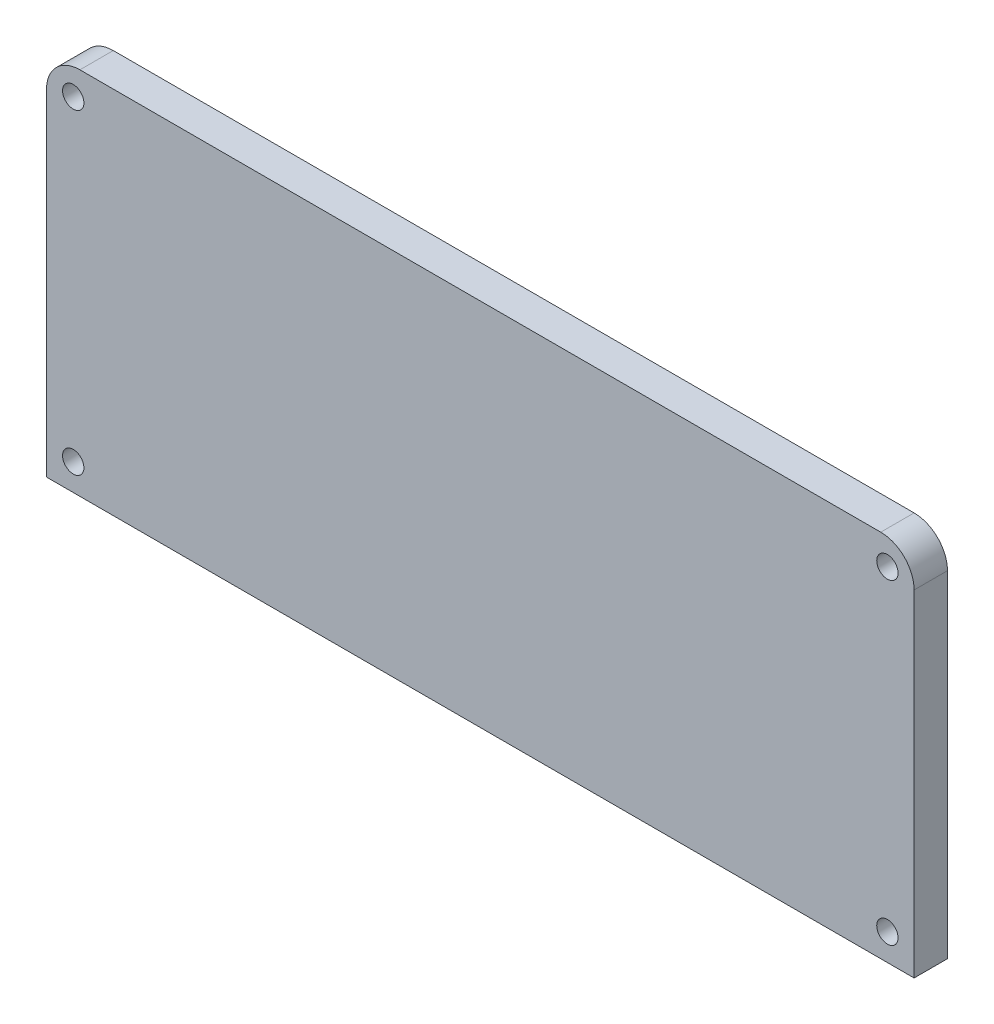
SolidWorks part; units mm, degrees
ref_plane "Front Plane" through (0, 0, 0) normal (0, 0, 1) x (1, 0, 0)
ref_plane "Top Plane" through (0, 0, 0) normal (0, 1, 0) x (1, 0, 0)
ref_plane "Right Plane" through (0, 0, 0) normal (1, 0, 0) x (0, 0, -1)
sketch "Sketch2" plane through (0, 0, 0) normal (1, 0, 0) x (0, 0, -1)
  line L0 (0, 0) -> (0, 20)
  line L1 (0, 20) -> (35.3553, 55.3553)
  line L2 (35.3553, 55.3553) -> (120, 55.3553)
  line L3 (120, 55.3553) -> (120, 0)
  line L4 (120, 0) -> (0, 0)
  dimension "D1" = 20
  dimension "D2" = 50
  dimension "D3" = 135
  dimension "D4" = 120
extrude "Boss-Extrude1" add sketch "Sketch2" along normal blind 130
shell "Shell1" thickness 5 removed face at (65, 27.6777, -120)
sketch "Sketch3" plane through (0, 10, 10) normal (0, 0.7071, 0.7071) x (1, 0, 0)
  line L0 (0, 64.1421) -> (0, 14.1421) construction
  line L1 (17, 52.3921) -> (90.1, 52.3921)
  line L2 (17, 52.3921) -> (17, 25.8921)
  line L3 (17, 25.8921) -> (90.1, 25.8921)
  line L4 (90.1, 52.3921) -> (90.1, 25.8921)
  circle A0 centre (108.1, 39.1421) radius 3.4
  point P6 (0, 39.1421)
  point P7 (17, 39.1421)
  point P11 (90.1, 39.1421)
  dimension "D3" = 6.8
  dimension "D1" = 73.1
  dimension "D2" = 26.5
  dimension "D4" = 18
  dimension "D5" = 17
extrude "Cut-Extrude1" cut sketch "Sketch3" against normal up to surface (5 mm away) up to face at (65, 34.1421, -21.2132)
fillet "Fillet1" radius 10 5 edges at (65, 20, 0) (65, 55.3553, -35.3553) (65, 50.3553, -37.4264) (65, 5, -5) (65, 17.9289, -5)
fillet "Fillet2" radius 5 10 edges at (0, 55.3553, -79.7487) (0, 54.5941, -35.6706) (0, 37.6777, -17.6777) (0, 19.6847, -0.7612) (130, 55.3553, -79.7487) (130, 54.5941, -35.6706) (130, 37.6777, -17.6777) (130, 19.6847, -0.7612) (0, 7.9289, 0) (130, 7.9289, 0)
sketch "Sketch4" plane through (130, 0, 0) normal (1, 0, 0) x (0, 0, -1)
  line L0 (5, 0) -> (120, 0) construction
  line L1 (108, 22) -> (112, 22)
  line L2 (106, 20) -> (106, 17)
  line L3 (108, 15) -> (112, 15)
  line L4 (114, 20) -> (114, 17)
  line L5 (120, 0) -> (120, 50.3553) construction
  arc A0 (106, 17) -> (108, 15) centre (108, 17) ccw
  arc A1 (112, 15) -> (114, 17) centre (112, 17) ccw
  arc A2 (112, 22) -> (114, 20) centre (112, 20) cw
  arc A3 (108, 22) -> (106, 20) centre (108, 20) ccw
  point P8 (114, 15)
  point P11 (114, 22)
  point P14 (106, 22)
  dimension "D3" = 2
  dimension "D1" = 8
  dimension "D2" = 7
  dimension "D4" = 15
  dimension "D5" = 6
extrude "Cut-Extrude2" cut sketch "Sketch4" against normal up to surface (5 mm away) up to face at (125, 27.4827, -48.7525)
fillet "Fillet3" radius 5 12 edges at (125, 7.7176, -8.1468) (125, 17.8922, -5.8816) (125, 34.1421, -21.2132) (125, 49.5941, -37.7417) (5, 7.7176, -8.1468) (5, 17.8922, -5.8816) (5, 34.1421, -21.2132) (5, 49.5941, -37.7417) (125, 5, -67.5) (125, 50.3553, -80.7843) (5, 5, -67.5) (5, 50.3553, -80.7843)
sketch "Sketch5" plane through (0, 10, 10) normal (0, 0.7071, 0.7071) x (1, 0, 0)
  line L0 (102.2, 33.1421) -> (114, 45.1421) construction
  line L1 (102.2, 45.1421) -> (114, 45.1421) construction
  line L2 (102.2, 45.1421) -> (102.2, 33.1421) construction
  line L3 (102.2, 33.1421) -> (114, 33.1421) construction
  line L4 (114, 45.1421) -> (114, 33.1421) construction
  line L6 (99.8, 55.0421) -> (118.6, 55.0421) construction
  line L7 (99.8, 55.0421) -> (99.8, 28.7421) construction
  line L8 (99.8, 28.7421) -> (118.6, 28.7421) construction
  line L9 (118.6, 55.0421) -> (118.6, 28.7421) construction
  circle A0 centre (108.1, 39.1421) radius 3.4 construction
  circle A1 centre (108.1, 39.1421) radius 3.4 construction
  circle A2 centre (116.3, 48.4421) radius 1.4
  circle A3 centre (116.3, 34.4421) radius 1.4
  point P8 (108.1, 39.1421)
  dimension "D7" = 2.8
  dimension "D1" = 12
  dimension "D2" = 11.8
  dimension "D3" = 2.4
  dimension "D4" = 18.8
  dimension "D5" = 26.3
  dimension "D6" = 4.4
  dimension "D8" = 14
  dimension "D9" = 5.7
  dimension "D10" = 16.5
extrude "Cut-Extrude3" cut sketch "Sketch5" against normal up to next
sketch "Sketch6" plane through (0, 10, 10) normal (0, 0.7071, 0.7071) x (1, 0, 0)
  line L0 (90.1, 52.3921) -> (17, 52.3921) construction
  line L1 (13.3, 57.3921) -> (93.8, 57.3921) construction
  line L2 (13.3, 57.3921) -> (13.3, 20.8921) construction
  line L3 (13.3, 20.8921) -> (93.8, 20.8921) construction
  line L4 (93.8, 57.3921) -> (93.8, 20.8921) construction
  line L5 (17, 52.3921) -> (17, 25.8921) construction
  circle A0 centre (15.8, 54.3921) radius 1.1
  circle A1 centre (90.8, 54.3921) radius 1.1
  circle A2 centre (90.8, 23.3921) radius 1.1
  circle A3 centre (15.8, 23.3921) radius 1.1
  point P16 (13.3, 39.1421)
  point P17 (17, 39.1421)
  point P19 (53.55, 57.3921)
  point P20 (53.55, 52.3921)
  dimension "D3" = 2.2
  dimension "D1" = 75
  dimension "D2" = 31
  dimension "D4" = 5
  dimension "D5" = 3.7
  dimension "D6" = 3
  dimension "D7" = 2.5
extrude "Cut-Extrude4" cut sketch "Sketch6" against normal up to next
sketch "Sketch7" plane through (0, 5, 0) normal (0, 1, 0) x (1, 0, 0)
  line L0 (109.5, 21.5) -> (113, 21.5) construction
  line L1 (113, 18) -> (13, 18) construction
  line L2 (113, 18) -> (113, 68) construction
  line L3 (113, 68) -> (13, 68) construction
  line L4 (13, 18) -> (13, 68) construction
  line L5 (109.5, 21.5) -> (109.5, 18) construction
  line L7 (16.5, 21.5) -> (13, 21.5) construction
  line L8 (16.5, 21.5) -> (16.5, 18) construction
  line L9 (109.5, 64.5) -> (109.5, 68) construction
  line L10 (10, 120) -> (10, 15) construction
  line L11 (10, 15) -> (120, 15) construction
  line L12 (120, 120) -> (10, 120) construction
  line L13 (111, 77) -> (51, 77) construction
  line L14 (111, 77) -> (111, 117) construction
  line L15 (111, 117) -> (51, 117) construction
  line L16 (51, 77) -> (51, 117) construction
  line L17 (109, 79) -> (109, 77) construction
  line L18 (109, 79) -> (111, 79) construction
  line L19 (53, 79) -> (51, 79) construction
  line L20 (109, 115) -> (109, 117) construction
  circle A0 centre (16.5, 21.5) radius 1.5
  circle A1 centre (16.5, 64.5) radius 1.5
  circle A2 centre (109.5, 21.5) radius 1.5
  circle A3 centre (109.5, 64.5) radius 1.5
  circle A4 centre (109, 79) radius 1.5
  circle A5 centre (53, 79) radius 1.5
  circle A6 centre (53, 115) radius 1.5
  circle A7 centre (109, 115) radius 1.5
  dimension "D1" = 3
  dimension "D12" = 2
  dimension "D2" = 43
  dimension "D3" = 93
  dimension "D4" = 100
  dimension "D5" = 50
  dimension "D6" = 3
  dimension "D7" = 3
  dimension "D8" = 40
  dimension "D9" = 60
  dimension "D10" = 2
  dimension "D11" = 3
  dimension "D13" = 2
extrude "Cut-Extrude5" cut sketch "Sketch7" against normal up to next
hole_wizard "CSK for M3 Countersunk Flat Head Screw2" positions "Sketch12" profile "Sketch13" countersink size "M3" standard "ISO"
sketch "Sketch12" plane through (0, 0, 0) normal (0, -1, 0) x (-1, 0, 0)
  point P0 (-109, 115)
  point P3 (-53, 115)
  point P6 (-53, 79)
  point P9 (-109, 79)
  point P12 (-16.5, 64.5)
  point P15 (-16.5, 21.5)
  point P18 (-109.5, 21.5)
  point P21 (-109.5, 64.5)
sketch "Sketch13" plane through (109, 0, -115) normal (1, 0, 0) x (0, 0, -1)
  line L0 (0, 0) -> (0, 8.9614)
  line L1 (0, 8.9614) -> (1.6, 8)
  line L2 (1.6, 8) -> (1.6, 1.55)
  line L3 (1.6, 1.55) -> (3.15, 0)
  line L5 (3.15, 0) -> (0, 0)
  line L6 (-1.6, 1.55) -> (-3.15, 0) construction
  line L10 (0, 8.9614) -> (-1.6, 8) construction
  line L11 (0, -6.35) -> (0, 107.95) construction
  dimension "Hole Dia." = 3.2
  dimension "Hole Depth" = 8
  dimension "Near C'Sink Dia." = 6.3
  dimension "Near C'Sink Angle" = 90
  dimension "Drill Angle" = 118
sketch "Sketch14" plane through (0, 0, 0) normal (-1, 0, 0) x (0, 0, 1)
  line L0 (-34, 14.5) -> (-30, 14.5) construction
  line L1 (-34, 18.5) -> (-30, 18.5)
  line L2 (-34, 10.5) -> (-30, 10.5)
  line L3 (-5, 0) -> (-120, 0) construction
  line L4 (-120, 0) -> (-120, 50.3553) construction
  line L5 (-19.9, 5) -> (-23.1, 5) construction
  line L6 (-19.9, 5) -> (-23.1, 5) construction
  arc A0 (-34, 18.5) -> (-34, 10.5) centre (-34, 14.5) ccw
  arc A1 (-30, 10.5) -> (-30, 18.5) centre (-30, 14.5) ccw
  point P2 (-32, 14.5)
  dimension "D1" = 4
  dimension "D2" = 4
  dimension "D3" = 14.5
  dimension "D4" = 86
extrude "Cut-Extrude6" cut sketch "Sketch14" against normal up to next
sketch "Sketch15" plane through (0, 0, -120) normal (0, 0, -1) x (-1, 0, 0)
  line L0 (-125, 55.3553) -> (-5, 55.3553) construction
  line L1 (-130, 0) -> (-130, 50.3553) construction
  line L2 (0, 0) -> (0, 50.3553) construction
  line L3 (-130, 0) -> (0, 0) construction
  circle A0 centre (-126, 51.3553) radius 1.2
  circle A1 centre (-126, 4) radius 1.2
  circle A2 centre (-4, 4) radius 1.2
  circle A3 centre (-4, 51.3553) radius 1.2
  dimension "D1" = 2.4
  dimension "D2" = 4
  dimension "D3" = 4
  dimension "D4" = 4
  dimension "D5" = 4
extrude "Cut-Extrude7" cut sketch "Sketch15" against normal blind 20
sketch "Sketch16" plane through (0, 0, -120) normal (0, 0, -1) x (-1, 0, 0)
  line L4 (0, 0) -> (0, 50.3553)
  line L5 (-5, 55.3553) -> (-125, 55.3553)
  line L6 (-130, 50.3553) -> (-130, 0)
  line L7 (-130, 0) -> (0, 0)
  line L8 (0, 0) -> (0, 50.3553)
  line L9 (-5, 55.3553) -> (-125, 55.3553)
  line L10 (-130, 50.3553) -> (-130, 0)
  line L11 (-130, 0) -> (0, 0)
  circle A0 centre (-126, 4) radius 1.2 construction
  circle A1 centre (-4, 4) radius 1.2 construction
  arc A2 (0, 50.3553) -> (-5, 55.3553) centre (-5, 50.3553) ccw
  arc A3 (-125, 55.3553) -> (-130, 50.3553) centre (-125, 50.3553) ccw
  arc A4 (0, 50.3553) -> (-5, 55.3553) centre (-5, 50.3553) ccw
  arc A5 (-125, 55.3553) -> (-130, 50.3553) centre (-125, 50.3553) ccw
  circle A6 centre (-4, 51.3553) radius 1.2 construction
  circle A7 centre (-126, 51.3553) radius 1.2 construction
  circle A8 centre (-126, 4) radius 1.2
  circle A9 centre (-4, 4) radius 1.2
  circle A10 centre (-4, 51.3553) radius 1.2
  circle A11 centre (-126, 51.3553) radius 1.2
  dimension "D1" = 0
extrude "Boss-Extrude2" add sketch "Sketch16" along normal blind 5 separate body
hole_wizard "CSK for M3 Countersunk Flat Head Screw3" positions "Sketch19" profile "Sketch20" countersink size "M3" standard "ISO"
sketch "Sketch19" plane through (0, 0, -125) normal (0, 0, -1) x (-1, 0, 0)
  point P0 (-126, 51.3553)
  point P3 (-126, 4)
  point P6 (-4, 51.3553)
  point P9 (-4, 4)
sketch "Sketch20" plane through (126, 51.3553, -125) normal (1, 0, 0) x (0, 1, 0)
  line L0 (0, 0) -> (0, 8.9614)
  line L1 (0, 8.9614) -> (1.6, 8)
  line L2 (1.6, 8) -> (1.6, 1.55)
  line L3 (1.6, 1.55) -> (3.15, 0)
  line L5 (3.15, 0) -> (0, 0)
  line L6 (-1.6, 1.55) -> (-3.15, 0) construction
  line L10 (0, 8.9614) -> (-1.6, 8) construction
  line L11 (0, -6.35) -> (0, 107.95) construction
  dimension "Hole Dia." = 3.2
  dimension "Hole Depth" = 8
  dimension "Near C'Sink Dia." = 6.3
  dimension "Near C'Sink Angle" = 90
  dimension "Drill Angle" = 118
delete or keep bodies "Body-Delete/Keep 1" type delete bodies bodies 110
